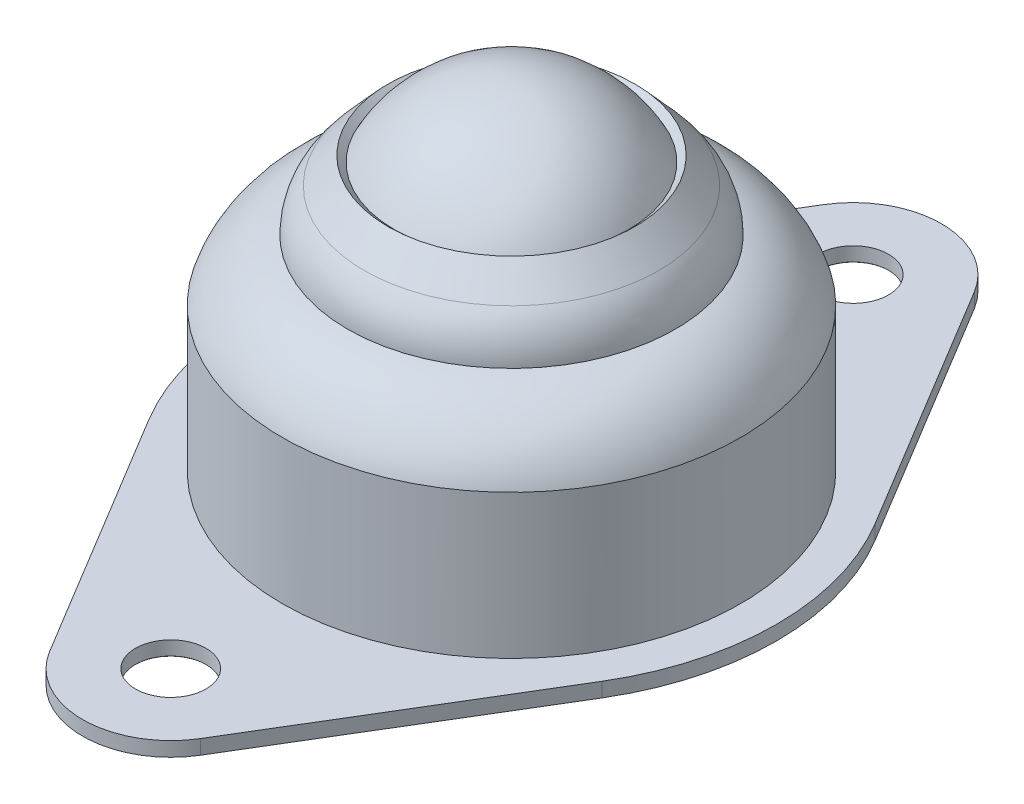
SolidWorks part; units mm, degrees
note: '?' marks a value the reader was unsure of.
material "AISI Type 316L stainless steel"
ref_plane "Front Plane" through (0, 0, 0) normal (0, 0, 1) x (1, 0, 0)
ref_plane "Top Plane" through (0, 0, 0) normal (0, 1, 0) x (1, 0, 0)
ref_plane "Right Plane" through (0, 0, 0) normal (1, 0, 0) x (0, 0, -1)
other "Configuration Table"
sketch "Sketch1" plane through (0, 0, 0) normal (0, 1, 0) x (1, 0, 0)
  line L0 (-4.2515, 21.934) -> (-12.8126, 7.7519)
  line L1 (4.3095, 21.934) -> (12.8706, 7.7519)
  line L2 (-14.971, 0) -> (15.029, 0) construction
  line L3 (0.029, 0) -> (0.029, 49.5109) construction
  line L4 (4.3095, -21.934) -> (12.8706, -7.7519)
  line L5 (-4.2515, -21.934) -> (-12.8126, -7.7519)
  arc A0 (-12.8126, 7.7519) -> (-12.8126, -7.7519) centre (0.029, 0) ccw
  arc A1 (4.3095, 21.934) -> (-4.2515, 21.934) centre (0.029, 19.35) ccw
  arc A2 (4.3095, -21.934) -> (-4.2515, -21.934) centre (0.029, -19.35) cw
  arc A3 (12.8706, -7.7519) -> (12.8706, 7.7519) centre (0.029, 0) ccw
  dimension "D1" = 5
  dimension "D2" = 15
  dimension "D3" = 38.7
extrude "base" add sketch "Sketch1" along normal blind 0.82
ref_axis "Mount1" through (0.029, 0.82, 19.35) along (0, -1, 0)?
ref_axis "Mount2" through (0.029, 14.9554, -19.35) along (0, -1, 0)?
hole_wizard "Ø4.0mm Dowel Hole1" positions "Sketch8" profile "Sketch7" hole size "Ø4.0" standard "ISO" end condition through all
sketch "Sketch8" plane through (0, 0, 0) normal (0, 1, 0) x (1, 0, 0)
  point P0 (0.029, -19.35)
  point P3 (0.029, 19.35)
sketch "Sketch7" plane through (0.029, 0, 19.35) normal (1, 0, 0) x (0, 0, -1)
  line L0 (0, 0) -> (0, 0.82)
  line L1 (0, 0.82) -> (2, 0.82)
  line L2 (2, 0.82) -> (2, 0.025)
  line L3 (2, 0.025) -> (2.025, 0)
  line L5 (2.025, 0) -> (0, 0)
  line L6 (-2, 0.025) -> (-2.025, 0) construction
  line L11 (0, -6.35) -> (0, 6.8057) construction
  dimension "Thru Hole Dia." = 4
  dimension "Thru Hole Depth" = 0.82
  dimension "Near C'Sink Dia." = 4.05
  dimension "Near C'Sink Angle" = 90
sketch "Sketch3" plane through (0, 0, 0) normal (1, 0, 0) x (0, 0, -1)
  line L0 (0, 0) -> (0, 19.6785) construction
  line L1 (0, 20) -> (0, 5)
  line L3 (7.7519, 0) -> (21.934, 0) construction
  arc A0 (0, 5) -> (0, 20) centre (0, 12.5) ccw
  dimension "D1" = 15
  dimension "D2" = 20
revolve "ball" add sketch "Sketch3" angle 360 about L0
sketch "Sketch5" plane through (0, 0, 0) normal (0, 0, 1) x (1, 0, 0)
  line L0 (0, 0) -> (0, 20) construction
  line L1 (12.5, 0.82) -> (12.5, 8.8994)
  line L2 (4.3095, 0.82) -> (12.8706, 0.82) construction
  line L5 (7.9757, 14.5114) -> (6.6332, 16)
  circle A0 centre (0, 12.5) radius 7.5 construction
  arc A1 (8.7724, 12.0316) -> (12.5, 8.8994) centre (8.0979, 7.4447) cw
  arc A2 (8.7724, 12.0316) -> (7.9757, 14.5114) centre (5.6196, 12.3866) ccw
  point P14 (12.5, 11)
  dimension "D1" = 25
  dimension "D2" = 11
  dimension "D3" = 13.6018
  dimension "D5" = 4
revolve "ball-casing" add sketch "Sketch5" angle 360 about L0
ref_plane "CONTACT" through (0, 20, 0) normal (0, 1, 0) x (1, 0, 0)
